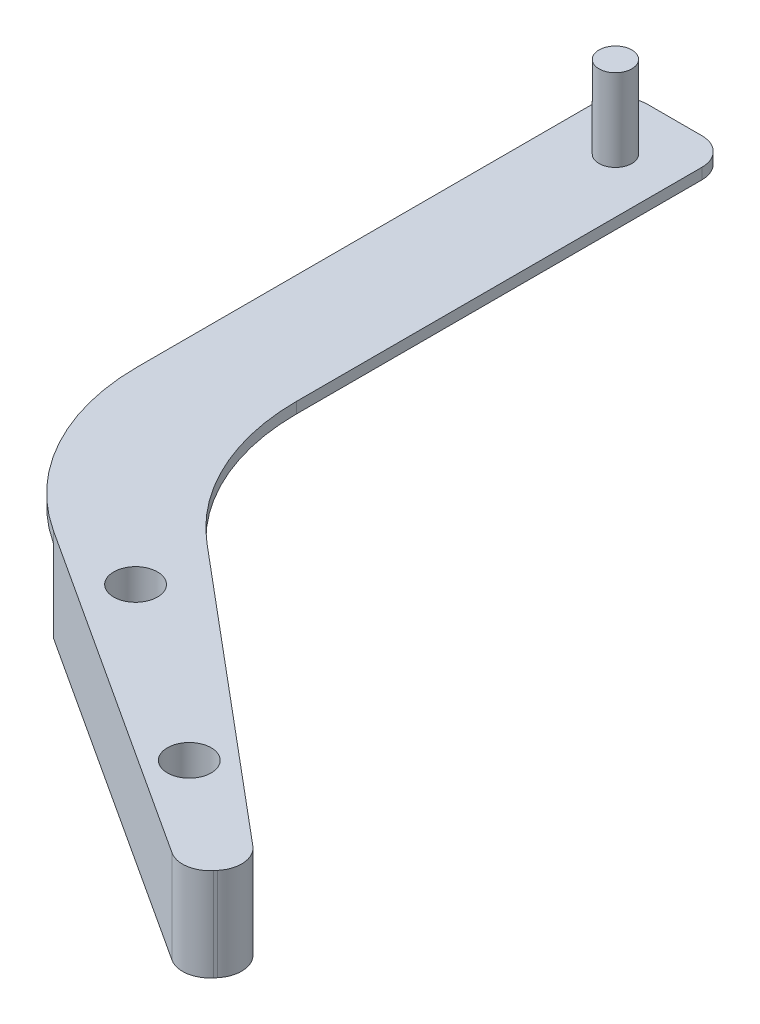
SolidWorks part; units mm, degrees
material "Alloy Steel"
ref_plane "Front" through (0, 0, 0) normal (0, 0, 1) x (1, 0, 0)
ref_plane "Top" through (0, 0, 0) normal (0, 1, 0) x (1, 0, 0)
ref_plane "Right" through (0, 0, 0) normal (1, 0, 0) x (0, 0, -1)
sketch "Sketch1" plane through (0, 0, 0) normal (0, 1, 0) x (1, 0, 0)
  line L0 (8.2144, -24.0096) -> (73.8671, -66.6449)
  line L1 (73.8671, -66.6449) -> (80.2949, -58.9845)
  line L2 (80.2949, -58.9845) -> (24.2885, -11.9895)
  line L3 (10, 18.6523) -> (10, 97.819)
  line L4 (10, 97.819) -> (-10, 97.819)
  line L5 (-10, 97.819) -> (-10, 9.5372)
  line L6 (0, 99.2423) -> (0, -26.7165) construction
  line L7 (-22.5148, 14.2291) -> (81.5665, -73.1055) construction
  line L8 (24.2885, -25.0435) -> (94.4077, -74.1415) construction
  arc A0 (8.2144, -24.0096) -> (-10, 9.5372) centre (30, 9.5372) cw
  arc A1 (24.2885, -11.9895) -> (10, 18.6523) centre (50, 18.6523) cw
  circle A2 centre (24.2885, -25.0435) radius 4
  circle A3 centre (57.0546, -47.9866) radius 4
  point P13 (18.3766, -20.0829)
  point P14 (58.6416, -49.0978)
  point P22 (-10, -12.181)
  point P25 (10, 0)
  dimension "D7" = 40
  dimension "D8" = 40
  dimension "D9" = 8
  dimension "D1" = 100
  dimension "D2" = 10
  dimension "D3" = 20
  dimension "D4" = 110
  dimension "D5" = 130
  dimension "D6" = 123
  dimension "D10" = 5
  dimension "D11" = 40
base flange "Base-Flange1" sketch "Sketch1" thickness 2 reverse thickness direction no parameters "D1"=0.7366
sketch "Sketch6" plane through (0, -2, 0) normal (0, -1, 0) x (1, 0, 0)
  line L0 (8.2144, 24.0096) -> (73.8671, 66.6449) construction
  line L1 (73.8671, 66.6449) -> (80.2949, 58.9845) construction
  line L2 (80.2949, 58.9845) -> (24.2885, 11.9895) construction
  line L3 (8.2144, 24.0096) -> (73.8671, 66.6449)
  line L4 (73.8671, 66.6449) -> (80.2949, 58.9845)
  line L5 (80.2949, 58.9845) -> (24.2885, 11.9895)
  line L6 (24.2885, 11.9895) -> (8.2144, 24.0096)
  circle A0 centre (24.2885, 25.0435) radius 4 construction
  circle A1 centre (57.0546, 47.9866) radius 4 construction
  circle A2 centre (24.2885, 25.0435) radius 4
  circle A3 centre (57.0546, 47.9866) radius 4
extrude "Boss-Extrude1" add sketch "Sketch6" along normal blind 15
sketch "Sketch7" plane through (0, 0, 0) normal (0, 1, 0) x (1, 0, 0)
  line L5 (-3, 87) -> (3, 87) construction
  line L6 (0, 84) -> (0, 90) construction
  line L8 (0, 41.4989) -> (0, 36.4989) construction
  line L9 (-10, 97.819) -> (-10, 9.5372) construction
  line L10 (10, 18.6523) -> (10, 97.819) construction
  circle A0 centre (0, 87) radius 3
  point P0 (0, 87)
  point P14 (3.4002, 89.0247)
  point P15 (0, 0)
  point P16 (1.8661, 87.524)
  dimension "D4" = 6
  dimension "D1" = 87
extrude "Boss-Extrude2" add sketch "Sketch7" along normal blind 15
fillet "Fillet2" radius 5 4 edges at (80.2949, -8.5, 58.9845) (73.8671, -8.5, 66.6449) (-10, -1, -97.819) (10, -1, -97.819)
sketch "Bend-Lines1" plane through (0, 0, 0) normal (0, 1, 0) x (1, 0, 0)
sketch "Bounding-Box1" plane through (0, 0, 0) normal (0, 1, 0) x (1, 0, 0)
sheet metal parameters "Sheet-Metal4" thickness 2 parameters "D1"=0.7366
flat pattern "Flat-Pattern4" [suppressed]
sketch "Bend-Lines2" plane through (0, 0, 0) normal (0, 1, 0) x (1, 0, 0)
sketch "Bounding-Box2" [suppressed] plane through (0, 0, 0) normal (0, 1, 0) x (1, 0, 0)
sheet metal parameters "Sheet-Metal5" thickness 2 parameters "D1"=0.7366
flat pattern "Flat-Pattern4"
sketch "Bend-Lines2" plane through (0, 0, 0) normal (0, 1, 0) x (1, 0, 0)
sketch "Bounding-Box2" [suppressed] plane through (0, 0, 0) normal (0, 1, 0) x (1, 0, 0)
sheet metal parameters "Sheet-Metal6" thickness 2 parameters "D1"=0.7366
flat pattern "Flat-Pattern4"
sketch "Bend-Lines2" plane through (0, 0, 0) normal (0, 1, 0) x (1, 0, 0)
sketch "Bounding-Box2" [suppressed] plane through (0, 0, 0) normal (0, 1, 0) x (1, 0, 0)
